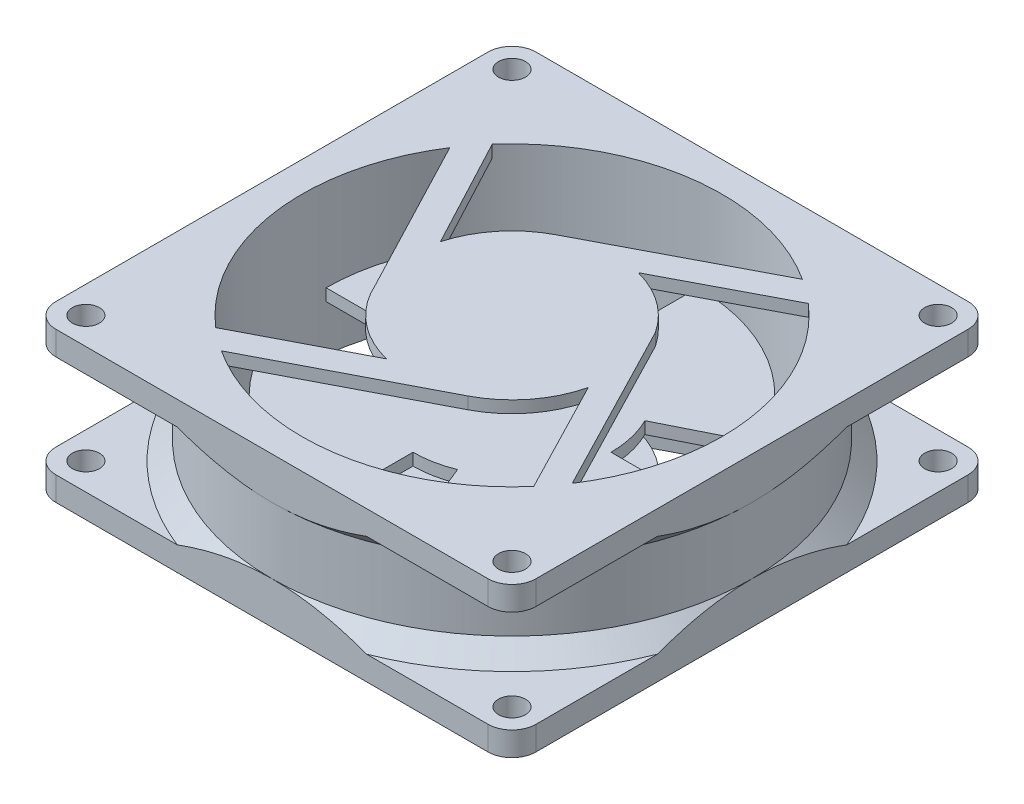
SolidWorks part; units mm, degrees
ref_plane "Спереди" through (0, 0, 0) normal (0, 0, 1) x (1, 0, 0)
ref_plane "Сверху" through (0, 0, 0) normal (0, 1, 0) x (1, 0, 0)
ref_plane "Справа" through (0, 0, 0) normal (1, 0, 0) x (0, 0, -1)
sketch "Эскиз1" plane through (0, 0, 0) normal (0, 1, 0) x (1, 0, 0)
  line L0 (-12.1394, 44.2395) -> (-12.1394, -35.7605) construction
  line L1 (-52.1394, 44.2395) -> (27.8606, 44.2395)
  line L2 (-52.1394, 44.2395) -> (-52.1394, -35.7605)
  line L3 (-52.1394, -35.7605) -> (27.8606, -35.7605)
  line L4 (27.8606, 44.2395) -> (27.8606, -35.7605)
  line L6 (27.8606, 4.2395) -> (-52.1394, 4.2395) construction
  dimension "D1" = 80
  dimension "D2" = 80
extrude "Бобышка-Вытянуть1" add sketch "Эскиз1" along normal blind 4
sketch "Эскиз3" plane through (0, 4, 0) normal (0, 1, 0) x (1, 0, 0)
  line L0 (-12.1394, 44.2395) -> (-12.1394, -35.7605) construction
  line L1 (27.8606, 44.2395) -> (-52.1394, 44.2395) construction
  line L2 (-52.1394, -35.7605) -> (27.8606, -35.7605) construction
  line L3 (-12.1394, -35.7605) -> (27.8606, 4.2395) construction
  line L4 (27.8606, -35.7605) -> (27.8606, 44.2395) construction
  line L5 (27.8606, 4.2395) -> (-52.1394, 4.2395) construction
  line L6 (-52.1394, 44.2395) -> (-52.1394, -35.7605) construction
  circle A0 centre (-12.1394, 4.2395) radius 40
extrude "Бобышка-Вытянуть2" add sketch "Эскиз3" along normal blind 17
sketch "Эскиз4" plane through (0, 21, 0) normal (0, 1, 0) x (1, 0, 0)
  line L1 (-52.1394, 44.2395) -> (27.8606, 44.2395)
  line L2 (-52.1394, 44.2395) -> (-52.1394, -35.7605)
  line L3 (-52.1394, -35.7605) -> (27.8606, -35.7605)
  line L4 (27.8606, 44.2395) -> (27.8606, -35.7605)
extrude "Бобышка-Вытянуть3" add sketch "Эскиз4" along normal blind 4
sketch "Эскиз5" plane through (0, 25, 0) normal (0, 1, 0) x (1, 0, 0)
  line L0 (-12.1394, 44.2395) -> (-12.1394, -35.7605) construction
  line L1 (27.8606, 44.2395) -> (-52.1394, 44.2395) construction
  line L2 (-52.1394, -35.7605) -> (27.8606, -35.7605) construction
  line L3 (-12.1394, -35.7605) -> (27.8606, 4.2395) construction
  line L4 (27.8606, -35.7605) -> (27.8606, 44.2395) construction
  line L5 (27.8606, 4.2395) -> (-52.1394, 4.2395) construction
  line L6 (-52.1394, 44.2395) -> (-52.1394, -35.7605) construction
  circle A0 centre (-12.1394, 4.2395) radius 35
  dimension "D1" = 70
extrude "Вырез-Вытянуть2" cut sketch "Эскиз5" against normal blind 38
sketch "Эскиз6" plane through (0, 25, 0) normal (0, 1, 0) x (1, 0, 0)
  line L0 (-12.1394, 44.2395) -> (-12.1394, -35.7605) construction
  line L1 (-47.6394, 39.7395) -> (23.3606, 39.7395) construction
  line L2 (-47.6394, 39.7395) -> (-47.6394, -31.2605) construction
  line L3 (-47.6394, -31.2605) -> (23.3606, -31.2605) construction
  line L4 (23.3606, 39.7395) -> (23.3606, -31.2605) construction
  line L5 (27.8606, 44.2395) -> (-52.1394, 44.2395) construction
  line L6 (-52.1394, -35.7605) -> (27.8606, -35.7605) construction
  line L7 (27.8606, 4.2395) -> (-52.1394, 4.2395) construction
  line L8 (27.8606, -35.7605) -> (27.8606, 44.2395) construction
  line L9 (-52.1394, 44.2395) -> (-52.1394, -35.7605) construction
  circle A0 centre (-47.6394, 39.7395) radius 2.25
  circle A1 centre (23.3606, 39.7395) radius 2.25
  circle A2 centre (-47.6394, -31.2605) radius 2.25
  circle A3 centre (23.3606, -31.2605) radius 2.25
  dimension "D5" = 4.5
  dimension "D6" = 4.5
  dimension "D7" = 4.5
  dimension "D8" = 4.5
  dimension "D1" = 71
  dimension "D2" = 71
  dimension "D3" = 35.5
  dimension "D4" = 35.5
extrude "Вырез-Вытянуть3" cut sketch "Эскиз6" against normal blind 38
fillet "Скругление1" radius 4 8 edges at (-52.1394, 23, 35.7605) (-52.1394, 2, 35.7605) (27.8606, 2, 35.7605) (27.8606, 23, 35.7605) (-52.1394, 23, -44.2395) (-52.1394, 2, -44.2395) (27.8606, 2, -44.2395) (27.8606, 23, -44.2395)
chamfer "Фаска3" distance 3 angle 45 8 edges at (16.1449, 4, 24.0448) (16.1449, 4, -32.5237) (-40.4236, 4, -32.5237) (-40.4236, 4, 24.0448) (16.1449, 21, -32.5237) (-40.4236, 21, -32.5237) (16.1449, 21, 24.0448) (-40.4236, 21, 24.0448)
ref_plane "Плоскость1" through (0, 12.5, 0) normal (0, 1, 0) x (1, 0, 0)
sketch "Эскиз7" plane through (0, 12.5, 0) normal (0, 1, 0) x (1, 0, 0)
  line L0 (-12.1394, 35.2033) -> (-12.1394, 20.7395)
  line L1 (-12.1394, -12.2605) -> (-12.1394, -26.7243)
  line L2 (18.8244, 4.2395) -> (4.3606, 4.2395)
  line L3 (-18.3502, 19.5259) -> (-23.7946, 32.9259)
  line L4 (-5.9285, -11.047) -> (-0.4841, -24.447)
  line L5 (15.5617, 18.0745) -> (2.622, 11.6119)
  line L6 (-26.9007, -3.133) -> (-39.8404, -9.5956)
  line L7 (-28.6394, 4.2395) -> (-43.1032, 4.2395)
  arc A0 (-23.7946, 32.9259) -> (-43.1032, 4.2395) centre (-12.1394, 4.2395) ccw
  arc A1 (-12.1394, 20.7395) -> (-18.3502, 19.5259) centre (-12.1394, 4.2395) ccw
  arc A2 (15.5617, 18.0745) -> (-12.1394, 35.2033) centre (-12.1394, 4.2395) ccw
  arc A3 (-0.4841, -24.447) -> (18.8244, 4.2395) centre (-12.1394, 4.2395) ccw
  arc A4 (-39.8404, -9.5956) -> (-12.1394, -26.7243) centre (-12.1394, 4.2395) ccw
  arc A5 (-28.6394, 4.2395) -> (-26.9007, -3.133) centre (-12.1394, 4.2395) ccw
  arc A6 (4.3606, 4.2395) -> (2.622, 11.6119) centre (-12.1394, 4.2395) ccw
  arc A7 (-12.1394, -12.2605) -> (-5.9285, -11.047) centre (-12.1394, 4.2395) ccw
  dimension "D1" = 33
extrude "Бобышка-Вытянуть4" add sketch "Эскиз7" along normal blind 1 and the other way blind 1 separate body
sketch "Эскиз8" plane through (0, 25, 0) normal (0, 1, 0) x (1, 0, 0)
  line L0 (-47.6394, 39.7395) -> (23.3606, -31.2605) construction
  line L1 (23.3606, -31.2605) -> (23.3606, 39.7395) construction
  line L2 (23.3606, 39.7395) -> (-47.6394, -31.2605) construction
  line L3 (8.1987, 34.3457) -> (-20.1349, 19.5206)
  line L6 (15.0119, -19.9024) -> (4.623, 0.1816)
  line L7 (-32.5875, -25.7921) -> (-4.1998, -11.0709)
  line L8 (-36.3295, -22.8688) -> (-16.3204, -12.4926)
  line L9 (-42.228, 24.6035) -> (-27.8625, -2.8475)
  line L10 (-39.1496, 28.539) -> (-28.7391, 8.9182)
  line L11 (12.0918, 31.311) -> (-7.7641, 20.9218)
  line L12 (17.8126, -16.3251) -> (2.2839, 13.6953)
  arc A0 (-27.8625, -2.8475) -> (-16.3204, -12.4926) centre (-12.1394, 4.2395) ccw
  arc A1 (15.0119, -19.9024) -> (17.8126, -16.3251) centre (-12.1394, 4.2395) ccw
  arc A7 (-20.1349, 19.5206) -> (-28.7391, 8.9182) centre (-12.1394, 4.2395) ccw
  arc A8 (2.2839, 13.6953) -> (-7.7641, 20.9218) centre (-12.1394, 4.2395) ccw
  arc A9 (-4.1998, -11.0709) -> (4.623, 0.1816) centre (-12.1394, 4.2395) ccw
  arc A10 (-36.3295, -22.8688) -> (-32.5875, -25.7921) centre (-12.1394, 4.2395) ccw
  arc A11 (-39.1496, 28.539) -> (-42.228, 24.6035) centre (-12.1394, 4.2395) ccw
  arc A12 (12.0918, 31.311) -> (8.1987, 34.3457) centre (-12.1394, 4.2395) ccw
extrude "Бобышка-Вытянуть5" add sketch "Эскиз8" against normal blind 2
sketch "Эскиз9" plane through (0, 0, 0) normal (0, -1, 0) x (1, 0, 0)
  line L0 (-31.2365, 25.0914) -> (-5.6197, 11.8072)
  line L1 (-5.9285, 11.047) -> (-0.4841, 24.447) construction
  line L2 (-35.0606, 22.2108) -> (-16.4194, 12.5439)
  line L3 (-16.3204, 12.4926) -> (-35.0606, 22.2108) construction
  line L4 (14.3545, 18.6314) -> (4.6747, -0.0816)
  line L5 (17.1145, 14.9755) -> (3.3561, -11.9785)
  line L6 (2.622, -11.6119) -> (15.5617, -18.0745) construction
  line L7 (6.8502, -33.6401) -> (-19.5146, -19.9113)
  line L8 (10.8279, -30.6497) -> (-7.667, -20.9726)
  line L9 (-7.7641, -20.9218) -> (10.8279, -30.6497) construction
  line L10 (-41.5227, -23.2558) -> (-28.2711, 2.0668)
  line L11 (-38.4831, -27.283) -> (-28.7892, -9.0126)
  line L12 (-28.7391, -8.9182) -> (-38.4831, -27.283) construction
  arc A0 (-28.7892, -9.0126) -> (-19.5146, -19.9113) centre (-12.1394, -4.2395) ccw
  arc A1 (-16.4194, 12.5439) -> (-28.2711, 2.0668) centre (-12.1394, -4.2395) ccw
  arc A2 (4.6747, -0.0816) -> (-5.6197, 11.8072) centre (-12.1394, -4.2395) ccw
  arc A3 (-7.667, -20.9726) -> (3.3561, -11.9785) centre (-12.1394, -4.2395) ccw
  arc A4 (6.8502, -33.6401) -> (10.8279, -30.6497) centre (-12.1394, -4.2395) ccw
  arc A5 (-41.5227, -23.2558) -> (-38.4831, -27.283) centre (-12.1394, -4.2395) ccw
  arc A6 (-31.2365, 25.0914) -> (-35.0606, 22.2108) centre (-12.1394, -4.2395) ccw
  arc A7 (17.1145, 14.9755) -> (14.3545, 18.6314) centre (-12.1394, -4.2395) ccw
extrude "Бобышка-Вытянуть6" add sketch "Эскиз9" against normal blind 2
